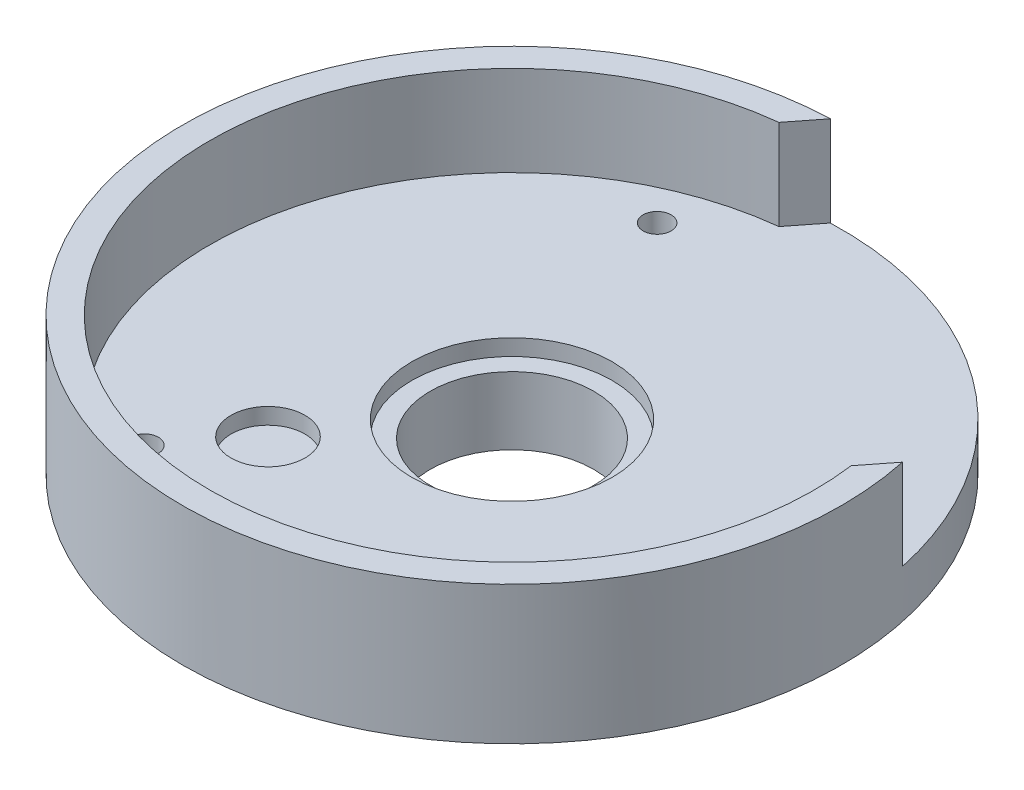
SolidWorks part; units mm, degrees
ref_plane "前视基准面" through (0, 0, 0) normal (0, 0, 1) x (1, 0, 0)
ref_plane "上视基准面" through (0, 0, 0) normal (0, 1, 0) x (1, 0, 0)
ref_plane "右视基准面" through (0, 0, 0) normal (1, 0, 0) x (0, 0, -1)
sketch "草图1" plane through (0, 0, 0) normal (0, 1, 0) x (1, 0, 0)
  line L0 (0, 0) -> (-11.8725, -15.1527)
  circle A0 centre (0, 0) radius 36.5
  circle A1 centre (0, 0) radius 11.1
  circle A2 centre (-11.8725, -15.1527) radius 4.1
extrude "凸台-拉伸1" add sketch "草图1" along normal blind 5.3 contours A0 A2 A1 region at (-35.4676, 0, 0)
sketch "草图2" plane through (0, 5.3, 0) normal (0, 1, 0) x (1, 0, 0)
  circle A1 centre (0, 0) radius 36.5
extrude "拉伸-薄壁1" add sketch "草图2" along normal blind 10 thin thin type one direction reverse wall 3
sketch "草图3" plane through (0, 0, 0) normal (0, -1, 0) x (1, 0, 0)
  circle A0 centre (-11.8725, 15.1527) radius 4.1
sketch "草图4" plane through (0, 0, 0) normal (0, -1, 0) x (1, 0, 0)
  circle A0 centre (-11.8725, 15.1527) radius 4.1
extrude "凸台-拉伸3" add sketch "草图4" along normal blind 5 separate body
sketch "草图5" plane through (0, 0, 0) normal (0, 1, 0) x (1, 0, 0)
  circle A0 centre (-11.8725, -15.1527) radius 4.1
extrude "凸台-拉伸4" add sketch "草图5" along normal blind 3.5
sketch "草图6" plane through (0, 5.3, 0) normal (0, 1, 0) x (1, 0, 0)
  line L0 (-11.8725, -15.1527) -> (0, 0)
  line L1 (0, 0) -> (22.5116, 28.7312)
  line L2 (-1.2232, 36.4795) -> (0, 0)
  line L3 (35.7129, 7.5392) -> (0, 0)
  line L4 (35.7129, 7.5392) -> (44.9642, 19.3465)
  line L5 (35.7129, 7.5392) -> (-1.2232, 36.4795)
  line L6 (44.9642, 19.3465) -> (8.0282, 48.2868)
  line L7 (8.0282, 48.2868) -> (-1.2232, 36.4795)
  line L8 (-1.2232, 36.4795) -> (-3.72, 33.2928)
  line L9 (-3.72, 33.2928) -> (33.216, 4.3525)
  line L10 (33.216, 4.3525) -> (35.7129, 7.5392)
  circle A0 centre (0, 0) radius 36.5 construction
  arc A1 (1.2265, 36.4794) -> (0.9939, 36.4865) centre (0, 0) ccw
  circle A3 centre (0, 0) radius 33.5 construction
  circle M8 centre (0, 0) radius 11.1
  circle M10 centre (0, 0) radius 33.5
extrude "切除-拉伸1" cut sketch "草图6" along normal blind 10 contours L3 L9 M10 | L10 L3 M10 | L9 L2 M10 | L6 L7 L5 L4 | L5 L1 M10 | L5 L1 M10 | L2 L8 M10 | L9 L2 L1 M8 | L9 L1 L3 M8 | L2 L1 M8 | L3 L1 M8 | L3 L5 L2 region at (2.2501, 5.3, -6.8926) region at (6.1542, 5.3, -3.8337) region at (5.0735, 5.3, -18.81) region at (17.0501, 5.3, -9.426) region at (-1.9696, 5.3, -32.668) region at (32.1906, 5.3, -5.9026) region at (-2.0174, 5.3, -34.4295) region at (13.1096, 5.3, -28.0853) region at (24.1337, 5.3, -19.4476) region at (33.9124, 5.3, -6.2776) region at (22.6679, 5.3, -28.9307)
sketch "草图7" plane through (0, 0, 0) normal (0, -1, 0) x (1, 0, 0)
  circle A0 centre (0, 0) radius 11.1
sketch "草图8" plane through (0, 0, 0) normal (0, -1, 0) x (1, 0, 0)
  circle A0 centre (0, 0) radius 12
extrude "凸台-拉伸7" add sketch "草图8" against normal blind 3.5
sketch "草图9" plane through (0, 0, 0) normal (0, -1, 0) x (1, 0, 0)
  circle A0 centre (0, 0) radius 11
  circle A1 centre (0, 0) radius 9.05
extrude "凸台-拉伸8" add sketch "草图9" along normal blind 4
sketch "草图10" plane through (0, -4, 0) normal (0, -1, 0) x (1, 0, 0)
  circle A0 centre (0, 0) radius 9.05
extrude "切除-拉伸2" cut sketch "草图10" against normal blind 10
sketch "草图11" plane through (0, 5.3, 0) normal (0, 1, 0) x (1, 0, 0)
  line L0 (0, 0) -> (-11.8725, -15.1527)
  line L1 (-11.8725, -15.1527) -> (-17.8859, -22.8275)
  circle A0 centre (0, 0) radius 29
  circle A1 centre (-17.8859, -22.8275) radius 1.55
  circle A2 centre (-10.8262, 26.9034) radius 1.55
  circle A3 centre (28.7121, -4.0759) radius 1.55
  point P13 (0, 0)
  dimension "D1" = 3
extrude "切除-拉伸3" cut sketch "草图11" against normal through all contours A0 A1 | A0 A1 L1 | L1 A1 A0 | A0 A3 | A0 A3 | A2 region at (-16.9623, 5.3, 22.706) region at (-17.9889, 5.3, 21.9017) region at (-18.287, 5.3, 23.3394) region at (28.0535, 5.3, 3.9824) region at (29.356, 5.3, 4.1673)
